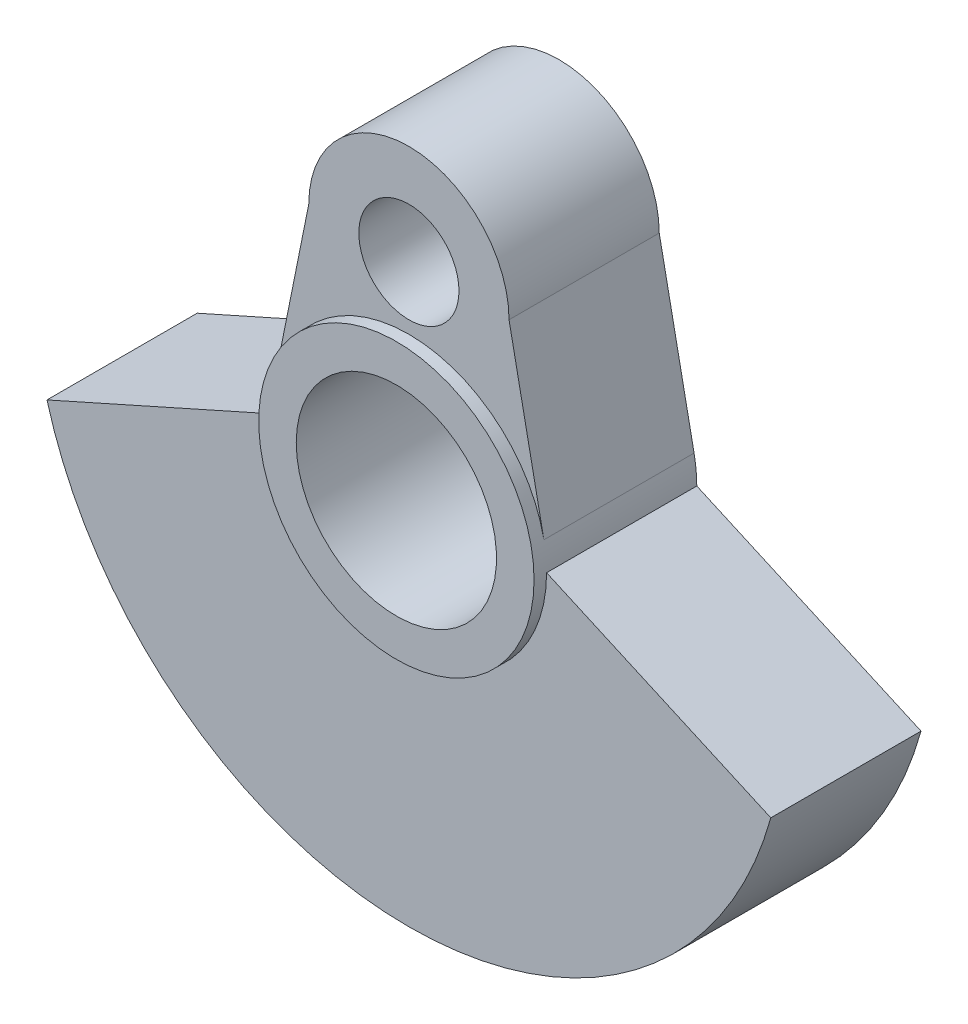
SolidWorks part; units mm, degrees
ref_plane "Front Plane" through (0, 0, 0) normal (0, 0, 1) x (1, 0, 0)
ref_plane "Top Plane" through (0, 0, 0) normal (0, 1, 0) x (1, 0, 0)
ref_plane "Right Plane" through (0, 0, 0) normal (1, 0, 0) x (0, 0, -1)
sketch "Sketch2" plane through (0, 0, 0) normal (0, 0, 1) x (1, 0, 0)
  line L0 (0, 0) -> (0, 16) construction
  line L1 (-4, 8) -> (-5.3919, 1.0853)
  line L2 (4, 8) -> (5.3919, 1.0853)
  line L3 (0, 0) -> (0, -12.5092) construction
  line L4 (-5.5, 0) -> (-14.4568, -4)
  line L7 (5.5, 0) -> (14.4568, -4)
  circle A0 centre (0, 0) radius 5.5
  circle A1 centre (0, 0) radius 4
  circle A2 centre (0, 8) radius 2
  arc A4 (-14.4568, -4) -> (14.4568, -4) centre (0, 0) ccw
  arc A5 (4, 8) -> (-4, 8) centre (0, 8) ccw
  point P4 (0, 8)
  dimension "D1" = 11
  dimension "D2" = 8
  dimension "D4" = 4
  dimension "D5" = 8
  dimension "D6" = 30
  dimension "D3" = 8
  dimension "D7" = 4
  dimension "D8" = 4
extrude "Boss-Extrude9" add sketch "Sketch2" along normal mid plane 6 contours L2 A5 L1 A0 A2 | L4 A4 L7 A0 region at (0, 11.8466, 0) region at (0, -7.8111, 0)
extrude "Boss-Extrude10" add sketch "Sketch2<9>" along normal blind 6.5 from surface contours A0 A1 region at (0, 5.3444, 0) starting at face at (0, -6.125, -3)
sketch "Sketch2<9>" plane through (0, 0, 0) normal (0, 0, 1) x (1, 0, 0) same geometry as "Sketch2"
